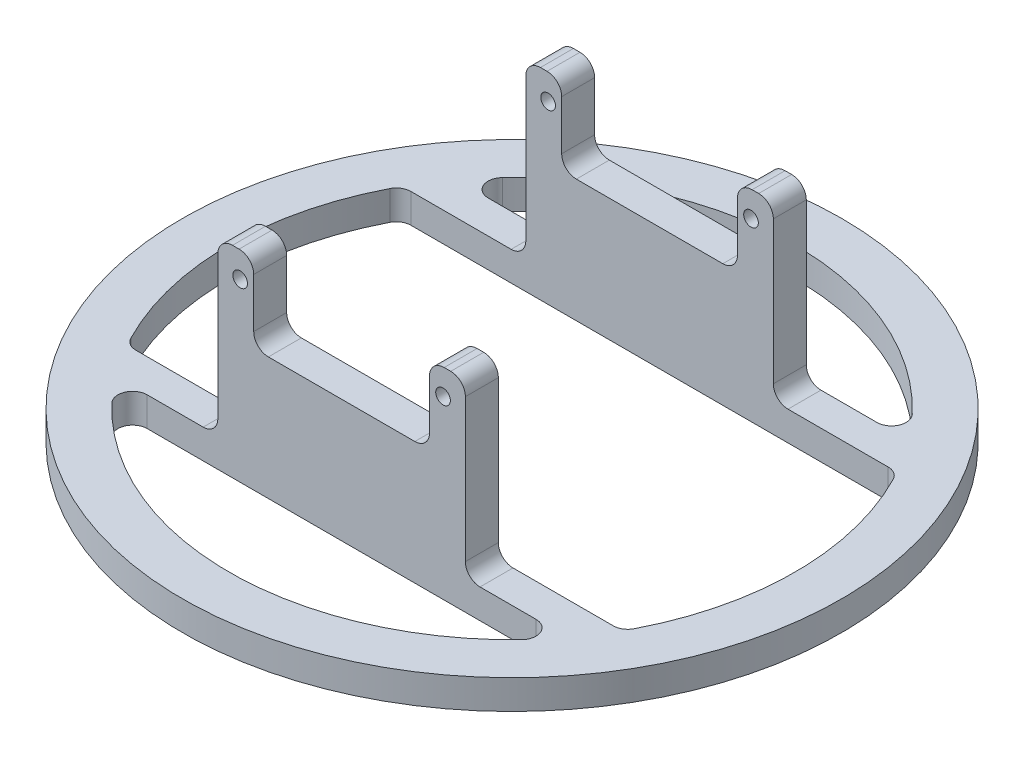
SolidWorks part; units mm, degrees
ref_plane "Front Plane" through (0, 0, 0) normal (0, 0, 1) x (1, 0, 0)
ref_plane "Top Plane" through (0, 0, 0) normal (0, 1, 0) x (1, 0, 0)
ref_plane "Right Plane" through (0, 0, 0) normal (1, 0, 0) x (0, 0, -1)
sketch "Sketch1" plane through (0, 0, 0) normal (0, 0, 1) x (1, 0, 0)
  line L0 (-13.85, 0) -> (13.85, 0) construction
  line L1 (-12, -6.25) -> (-12, 6.25) construction
  line L2 (15.9, -6.25) -> (-15.9, -6.25) construction
  line L3 (15.9, -6.25) -> (15.9, 6.25) construction
  line L4 (15.9, 6.25) -> (-15.9, 6.25) construction
  line L5 (-15.9, -6.25) -> (-15.9, 6.25) construction
  line L6 (12, 3.5) -> (16.9, 3.5)
  line L7 (12, 3.5) -> (12, -7.25)
  line L8 (11.5, -6.25) -> (-11.5, -6.25) construction
  line L9 (11.5, -6.25) -> (11.5, 6.25) construction
  line L10 (11.5, 6.25) -> (-11.5, 6.25) construction
  line L11 (-11.5, -6.25) -> (-11.5, 6.25) construction
  line L12 (16.9, 3.5) -> (16.9, -20)
  line L14 (-12, 3.5) -> (-16.9, 3.5)
  line L15 (-16.9, 3.5) -> (-16.9, -20)
  line L16 (-16.9, -20) -> (16.9, -20)
  line L17 (0, -20) -> (0, 0) construction
  line L18 (-12, 3.5) -> (-12, -7.25)
  line L19 (-12, -7.25) -> (12, -7.25)
  circle A0 centre (13.85, 0) radius 1
  circle A1 centre (-13.85, 0) radius 1
  point P5 (0, 0)
  point P6 (0, 0)
  point P31 (0, -7.25)
  dimension "D1" = 2
  dimension "D2" = 27.7
  dimension "D3" = 12.5
  dimension "D4" = 31.8
  dimension "D5" = 23
  dimension "D6" = 0.5
  dimension "D7" = 1
  dimension "D8" = 1
  dimension "D9" = 3.5
  dimension "D10" = 20
extrude "Boss-Extrude1" add sketch "Sketch1" along normal blind 4.5
ref_plane "Plane1" through (0, 0, -15.6) normal (0, 0, -1) x (-1, 0, 0)
ref_plane "Plane2" through (0, 0, -21.95) normal (0, 0, -1) x (-1, 0, 0)
ref_plane "Plane3" through (0, 0, -18.775) normal (0, 0, -1) x (-1, 0, 0)
ref_plane "Plane4" through (0, -20, 0) normal (0, -1, 0) x (-1, 0, 0)
sketch "Sketch4" plane through (0, -20, 0) normal (0, -1, 0) x (-1, 0, 0)
  line L0 (0, 0) -> (0, 18.775) construction
  line L1 (55, 18.775) -> (-55, 18.775) construction
  line L2 (16.9, -4.5) -> (16.9, 0) construction
  line L3 (16.9, -4.5) -> (-16.9, -4.5) construction
  line L4 (-16.9, -4.5) -> (-16.9, 0) construction
  line L5 (16.9, 0) -> (-16.9, 0) construction
  line L6 (16.9, -4.5) -> (16.9, 0) construction
  line L7 (16.9, -4.5) -> (-16.9, -4.5) construction
  line L8 (-16.9, -4.5) -> (-16.9, 0) construction
  line L9 (16.9, 0) -> (-16.9, 0) construction
  line L10 (-33.7835, 0) -> (33.7835, 0)
  line L11 (-30.8561, -4.5) -> (30.8561, -4.5)
  line L12 (-38.65, 18.775) -> (38.65, 18.775) construction
  line L13 (-30.8561, 42.05) -> (30.8561, 42.05)
  line L14 (-33.7835, 37.55) -> (33.7835, 37.55)
  circle A0 centre (0, 18.775) radius 45
  arc A1 (30.8561, 42.05) -> (-30.8561, 42.05) centre (0, 18.775) ccw
  arc A2 (-33.7835, 37.55) -> (-33.7835, 0) centre (0, 18.775) ccw
  arc A3 (-30.8561, -4.5) -> (30.8561, -4.5) centre (0, 18.775) ccw
  arc A4 (33.7835, 0) -> (33.7835, 37.55) centre (0, 18.775) ccw
  dimension "D1" = 90
  dimension "D2" = 6.35
sketch "Sketch2" plane through (0, -20, 0) normal (0, -1, 0) x (-1, 0, 0)
  line L0 (0, 0) -> (0, 18.775) construction
  line L1 (55, 18.775) -> (-55, 18.775) construction
  line L2 (-16.9, -4.5) -> (-16.9, 0) construction
  line L3 (-16.9, -4.5) -> (-16.9, 0)
  line L4 (16.9, -4.5) -> (-16.9, -4.5) construction
  line L5 (16.9, -4.5) -> (16.9, 0) construction
  line L6 (16.9, -4.5) -> (-16.9, -4.5)
  line L7 (16.9, -4.5) -> (16.9, 0)
  line L8 (0, 18.775) -> (28.7634, 18.775) construction
  line L9 (16.9, 42.05) -> (-16.9, 42.05)
  circle A0 centre (0, 18.775) radius 28.7634
extrude "Boss-Extrude3" add sketch "Sketch4" along normal blind 4
mirror "Mirror2" about plane through (0, 0, -18.775) normal (0, 0, -1) of "Boss-Extrude1"
fillet "Fillet2" radius 2 12 edges at (-12, -7.25, -39.8) (12, -7.25, -39.8) (-12, -7.25, 2.25) (12, -7.25, 2.25) (-33.7835, -22, 0) (-33.7835, -22, -37.55) (-30.8561, -22, 4.5) (30.8561, -22, 4.5) (33.7835, -22, 0) (33.7835, -22, -37.55) (-30.8561, -22, -42.05) (30.8561, -22, -42.05)
fillet "Fillet3" radius 2 12 edges at (-16.9, 3.5, 2.25) (-12, 3.5, 2.25) (12, 3.5, 2.25) (16.9, 3.5, 2.25) (-16.9, 3.5, -39.8) (-12, 3.5, -39.8) (12, 3.5, -39.8) (16.9, 3.5, -39.8) (16.9, -20, 2.25) (-16.9, -20, 2.25) (-16.9, -20, -39.8) (16.9, -20, -39.8)
ref_plane "Plane5" through (0, -1.875, 0) normal (0, 1, 0) x (1, 0, 0)
ref_plane "Plane6" through (0, 0, 0) normal (-1, 0, 0) x (0, 0, 1)
ref_axis "Axis1" through (0, -1.875, -42.275) along (0, 0, 1)
